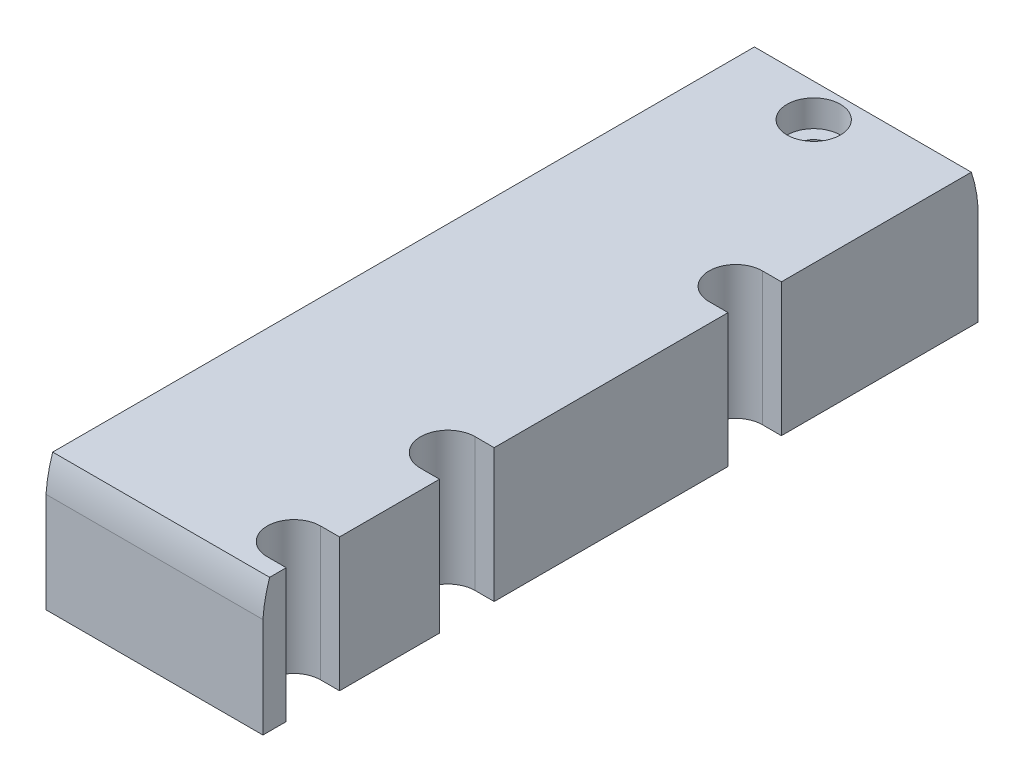
SolidWorks part; units mm, degrees
ref_plane "Front Plane" through (0, 0, 0) normal (0, 0, 1) x (1, 0, 0)
ref_plane "Top Plane" through (0, 0, 0) normal (0, 1, 0) x (1, 0, 0)
ref_plane "Right Plane" through (0, 0, 0) normal (1, 0, 0) x (0, 0, -1)
ref_plane "Plane1" through (0, 0, 0) normal (0, 1, 0) x (1, 0, 0)
sketch "Sketch1" plane through (0, 0, 0) normal (0, 1, 0) x (1, 0, 0)
  line L0 (-0.4, -53.65) -> (32.15, -53.65)
  line L1 (32.15, -53.65) -> (32.15, 53.65)
  line L2 (32.15, 53.65) -> (-0.4, 53.65)
  line L3 (-0.4, 53.65) -> (-0.4, -53.65)
  circle A0 centre (13.5, 47.65) radius 2
extrude "Boss-Extrude1" add sketch "Sketch1" along normal blind 20
ref_plane "Plane2" through (0, 0, 0) normal (1, 0, 0) x (0, 0, -1)
sketch "Sketch2" plane through (0, 0, 0) normal (1, 0, 0) x (0, 0, -1)
  line L0 (-53.65, 36.7751) -> (-53.65, 15.0133)
  line L1 (-33.7, 33.6) -> (-33.7, 36.7751)
  line L2 (-33.7, 36.7751) -> (-53.65, 36.7751)
  arc A0 (-53.65, 15.0133) -> (-33.7, 33.6) centre (-33.7, 13.6) cw
extrude "Cut-Extrude1" cut sketch "Sketch2" against normal blind 35 and the other way blind 35
ref_plane "Plane3" through (0, 0, 0) normal (1, 0, 0) x (0, 0, -1)
sketch "Sketch3" plane through (0, 0, 0) normal (1, 0, 0) x (0, 0, -1)
  line L0 (33.7, 36.7751) -> (33.7, 33.6)
  line L1 (53.65, 15.0133) -> (53.65, 36.7751)
  line L2 (53.65, 36.7751) -> (33.7, 36.7751)
  arc A0 (33.7, 33.6) -> (53.65, 15.0133) centre (33.7, 13.6) cw
extrude "Cut-Extrude2" cut sketch "Sketch3" against normal blind 35 and the other way blind 35
ref_plane "Plane4" through (0, 20, 0) normal (0, 1, 0) x (1, 0, 0)
sketch "Sketch4" plane through (0, 20, 0) normal (0, 1, 0) x (1, 0, 0)
  circle A0 centre (13.5, 47.65) radius 4
extrude "Cut-Extrude3" cut sketch "Sketch4" against normal blind 4
ref_plane "Plane5" through (0, 20, 0) normal (0, 1, 0) x (1, 0, 0)
sketch "Sketch5" plane through (0, 20, 0) normal (0, 1, 0) x (1, 0, 0)
  line L0 (29.3, -27.15) -> (32.15, -27.15)
  line L1 (32.15, -27.15) -> (32.15, -42.15)
  line L2 (32.15, -42.15) -> (29.3, -42.15)
  line L3 (29.3, -50.15) -> (32.15, -50.15)
  line L4 (32.15, -50.15) -> (32.15, -53.65)
  line L5 (32.15, -53.65) -> (50, -53.65)
  line L6 (50, -53.65) -> (50, 53.65)
  line L7 (50, 53.65) -> (32.15, 53.65)
  line L8 (32.15, 53.65) -> (32.15, 24.15)
  line L9 (32.15, 24.15) -> (29.3, 24.15)
  line L10 (29.3, 16.15) -> (32.15, 16.15)
  line L11 (32.15, 16.15) -> (32.15, -18.95)
  line L12 (32.15, -18.95) -> (29.3, -18.95)
  arc A0 (29.3, -18.95) -> (29.3, -27.15) centre (29.3, -23.05) ccw
  arc A1 (29.3, -42.15) -> (29.3, -50.15) centre (29.3, -46.15) ccw
  arc A2 (29.3, 24.15) -> (29.3, 16.15) centre (29.3, 20.15) ccw
extrude "Cut-Extrude4" cut sketch "Sketch5" against normal blind 21 and the other way blind 21
